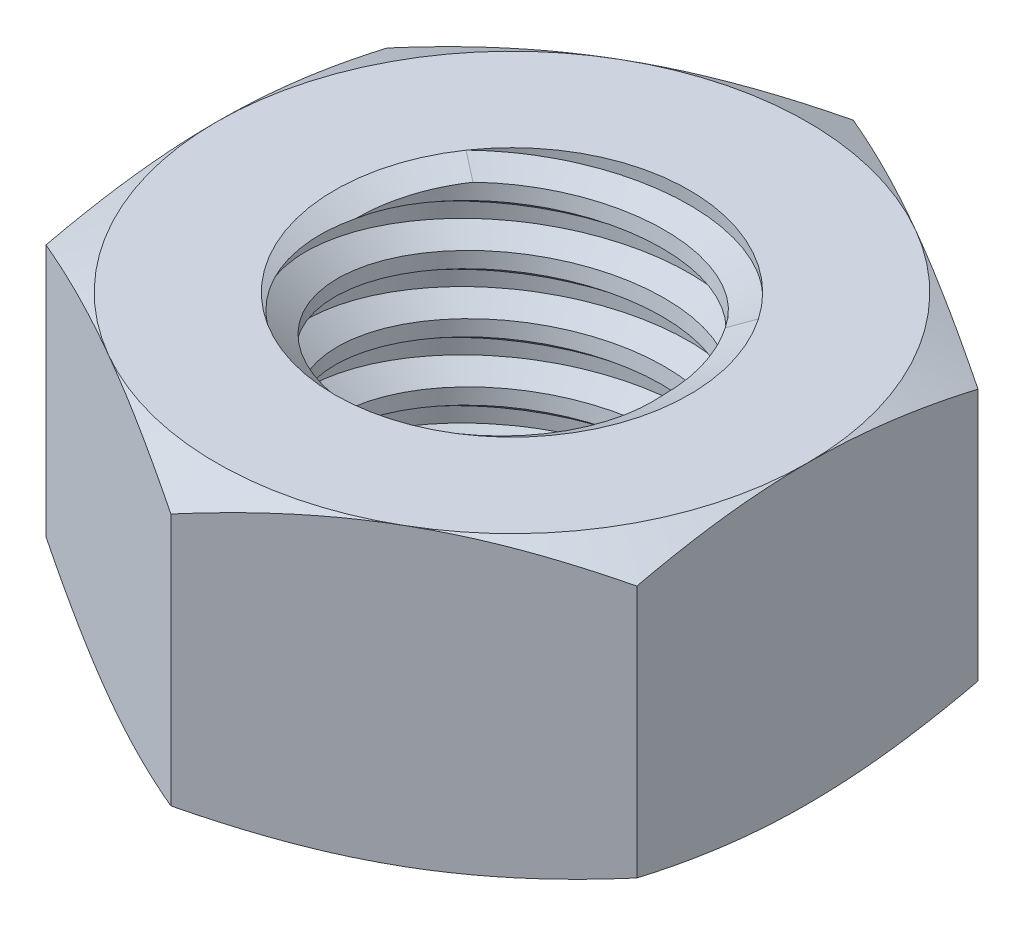
SolidWorks part; units mm, degrees
ref_plane "Front" through (0, 0, 0) normal (0, 0, 1) x (1, 0, 0)
ref_plane "Top" through (0, 0, 0) normal (0, 1, 0) x (1, 0, 0)
ref_plane "Right" through (0, 0, 0) normal (1, 0, 0) x (0, 0, -1)
sketch "Sketch1" plane through (0, 0, 0) normal (0, 1, 0) x (1, 0, 0)
  line L1 (0, 5.7735) -> (-5, 2.8868)
  line L2 (-5, 2.8868) -> (-5, -2.8868)
  line L3 (-5, -2.8868) -> (0, -5.7735)
  line L4 (0, -5.7735) -> (5, -2.8868)
  line L5 (5, -2.8868) -> (5, 2.8868)
  line L6 (5, 2.8868) -> (0, 5.7735)
  circle A0 centre (0, 0) radius 5 construction
  dimension "Hex Flats" = 10
extrude "Extrude1" add sketch "Sketch1" along normal mid plane 5
sketch "Sketch2" plane through (0, 0, 0) normal (1, 0, 0) x (0, 0, -1)
  line L0 (-3, -2.5) -> (-3, 2.5) construction
  line L1 (0, -2.5) -> (3, -2.5)
  line L2 (0, -2.5) -> (0, 2.5)
  line L3 (0, 2.5) -> (3, 2.5)
  line L4 (3, -2.5) -> (3, 2.5)
  line L5 (-2.8868, 2.5) -> (2.8868, 2.5) construction
  line L6 (-2.8868, -2.5) -> (2.8868, -2.5) construction
  line L7 (0, -5.5) -> (0, -2.5) construction
  dimension "Thread Dia" = 6
revolve "Revolve1" add sketch "Sketch2" angle 360 about L7
sketch "Sketch3" plane through (0, 0, 0) normal (1, 0, 0) x (0, 0, -1)
  line L0 (3, 2.5) -> (-3, 2.5) construction
  line L1 (-3, 2.5) -> (-3, 1.5) construction
  line L2 (-3, 1.5) -> (3, 2.5) construction
  line L3 (3, 2.5) -> (3.0205, 2.3767) construction
  line L4 (3.0205, 2.3767) -> (3.1644, 1.5136) construction
  line L5 (3.1644, 1.5136) -> (2.5791, 1.7329) construction
  line L6 (2.5791, 1.7329) -> (2.538, 1.9795) construction
  line L7 (2.538, 1.9795) -> (3.0205, 2.3767) construction
  line L8 (2.5586, 1.8562) -> (3.0925, 1.9452) construction
  line L9 (3, 2.5) -> (3, 1.9297) construction
  line L10 (3, 1.9297) -> (-3, 0.9297) construction
  line L11 (-3, 0.9297) -> (-3, 1.5) construction
  line L12 (-0.1784, 2.5) -> (0.1784, 0.3595) construction
  line L13 (-3, -2.5) -> (-3, 2.5) construction
  line L14 (0, 2.5) -> (3, 2.5) construction
  line L15 (3, -2.5) -> (3, 2.5) construction
  line L16 (0, 0) -> (0, 2.5) construction
  line L17 (-3.0205, 2.3767) -> (-3.1644, 1.5136)
  line L18 (-2.538, 1.9795) -> (-3.0205, 2.3767)
  line L19 (-2.5791, 1.7329) -> (-2.538, 1.9795)
  line L20 (-3.1644, 1.5136) -> (-2.5791, 1.7329)
  line L21 (0.1784, 2.5) -> (-0.1784, 0.3595) construction
  point P13 (0, 1.4297)
  dimension "D1" = 0.125
  dimension "D2" = 0.25
  dimension "Thread Pitch" = 1
  dimension "D4" = 60
  dimension "D5" = 1
revolve "Cut-Revolve1" cut sketch "Sketch3" angle 360 about L21
pattern_linear "LPattern1" count 5 spacing 1 along (0, -1, 0) count 2 spacing 1 along (0, 1, 0) of "Cut-Revolve1"
sketch "Sketch4" plane through (0, 0, 0) normal (1, 0, 0) x (0, 0, -1)
  line L0 (0, 2.5) -> (3, 2.5)
  line L1 (3, 2.5) -> (2.538, 2.2846)
  line L2 (2.538, 2.2846) -> (2.538, -2.2846)
  line L3 (2.538, -2.2846) -> (3, -2.5)
  line L4 (3, -2.5) -> (0, -2.5)
  line L5 (0, -2.5) -> (0, 2.5)
  line L6 (3, -2.5) -> (3, 2.5) construction
  line L7 (0, 2.5) -> (3, 2.5) construction
  line L8 (0, -2.5) -> (3, -2.5) construction
  line L9 (0, -2.5) -> (0, 2.5) construction
  line L10 (0, 2.5) -> (0, 3.0097) construction
  dimension "D1" = 25
revolve "Cut-Revolve2" cut sketch "Sketch4" angle 360 about L10
combine bodies "Combine1" operation type subtract main body 112 bodies to subtract 111
sketch "Sketch5" plane through (0, 0, 0) normal (1, 0, 0) x (0, 0, -1)
  line L0 (0, -2.5) -> (5, -2.5)
  line L1 (5, -2.5) -> (5.7735, -2.1393)
  line L2 (5.7735, -2.1393) -> (5.7735, 2.1393)
  line L3 (5.7735, 2.1393) -> (5, 2.5)
  line L4 (0, 2.5) -> (0, 3.77)
  line L5 (0, 3.77) -> (7.0435, 3.77)
  line L6 (7.0435, 3.77) -> (7.0435, -3.77)
  line L7 (7.0435, -3.77) -> (0, -3.77)
  line L8 (0, -3.77) -> (0, -2.5)
  line L9 (5, 2.5) -> (5, -2.5) construction
  line L11 (0, -2.5) -> (3, -2.5) construction
  line L12 (5, 2.5) -> (0, 2.5)
  line L13 (5.7735, 0) -> (7.0435, 0) construction
  line L14 (5.7735, 2.5) -> (5.7735, -2.5) construction
  line L15 (0, -2.5) -> (0, 2.5) construction
  line L17 (0, 0) -> (5, 0) construction
  line L22 (0, 2.5) -> (3, 2.5) construction
  dimension "D1" = 25
  dimension "D2" = 1.27
  dimension "D3" = 5
revolve "Cut-Revolve3" cut sketch "Sketch5" angle 360 about L15
equation "\"D1@Sketch3\"=\"Thread Pitch@Sketch3\"/8"
equation "\"D2@Sketch3\"=\"Thread Pitch@Sketch3\"/4"
equation "\"D5@Sketch3\"=\"Thread Pitch@Sketch3\""
equation "\"D4@LPattern1\"=\"Thread Pitch@Sketch3\""
equation "\"D3@LPattern1\"=\"Thread Pitch@Sketch3\""
equation "\"D1@LPattern1\"=\"Height@Extrude1\"/\"Thread Pitch@Sketch3\""
